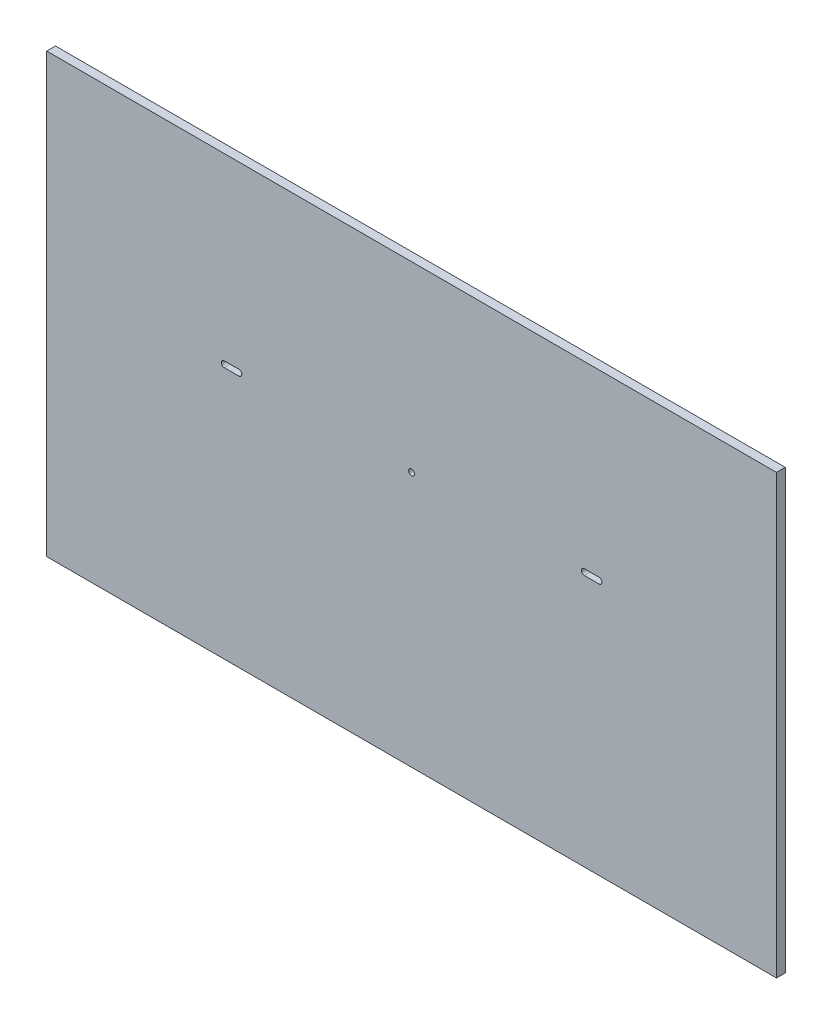
SolidWorks part; units mm, degrees
ref_plane "Front Plane" through (0, 0, 0) normal (0, 0, 1) x (1, 0, 0)
ref_plane "Top Plane" through (0, 0, 0) normal (0, 1, 0) x (1, 0, 0)
ref_plane "Right Plane" through (0, 0, 0) normal (1, 0, 0) x (0, 0, -1)
sketch "Sketch1" plane through (0, 0, 0) normal (0, 0, 1) x (1, 0, 0)
  line L1 (-500, -300) -> (500, -300)
  line L2 (-500, -300) -> (-500, 300)
  line L3 (-500, 300) -> (500, 300)
  line L4 (500, -300) -> (500, 300)
  line L5 (-500, -300) -> (500, 300) construction
  line L6 (-500, 300) -> (500, -300) construction
  point P0 (0, 0)
  dimension "D1" = 1000
  dimension "D2" = 600
extrude "Boss-Extrude1" add sketch "Sketch1" along normal blind 12
sketch "Sketch2" plane through (0, 0, 12) normal (0, 0, 1) x (1, 0, 0)
  line L0 (0, 300) -> (0, -300) construction
  line L1 (500, 300) -> (-500, 300) construction
  line L2 (-500, -300) -> (500, -300) construction
  line L3 (-500, 50) -> (500, 50) construction
  line L4 (-500, 300) -> (-500, -300) construction
  line L5 (500, -300) -> (500, 300) construction
  line L6 (-256.731, 50) -> (-236.731, 50) construction
  line L7 (-256.731, 54.05) -> (-236.731, 54.05)
  line L8 (-256.731, 45.95) -> (-236.731, 45.95)
  line L9 (256.731, 50) -> (236.731, 50) construction
  line L10 (256.731, 54.05) -> (236.731, 54.05)
  line L11 (256.731, 45.95) -> (236.731, 45.95)
  circle A0 centre (0, 50) radius 4.05
  circle A1 centre (-246.731, 50) radius 4.05 construction
  circle A2 centre (246.731, 50) radius 4.05 construction
  arc A3 (-256.731, 54.05) -> (-256.731, 45.95) centre (-256.731, 50) ccw
  arc A4 (-236.731, 45.95) -> (-236.731, 54.05) centre (-236.731, 50) ccw
  arc A5 (256.731, 54.05) -> (256.731, 45.95) centre (256.731, 50) cw
  arc A6 (236.731, 45.95) -> (236.731, 54.05) centre (236.731, 50) cw
  point P12 (0, 50)
  point P21 (-246.731, 50)
  point P29 (246.731, 50)
  dimension "D2" = 8.1
  dimension "D5" = 20
  dimension "D1" = 250
  dimension "D3" = 246.731
  dimension "D4" = 8.1
extrude "Cut-Extrude1" cut sketch "Sketch2" against normal through all
